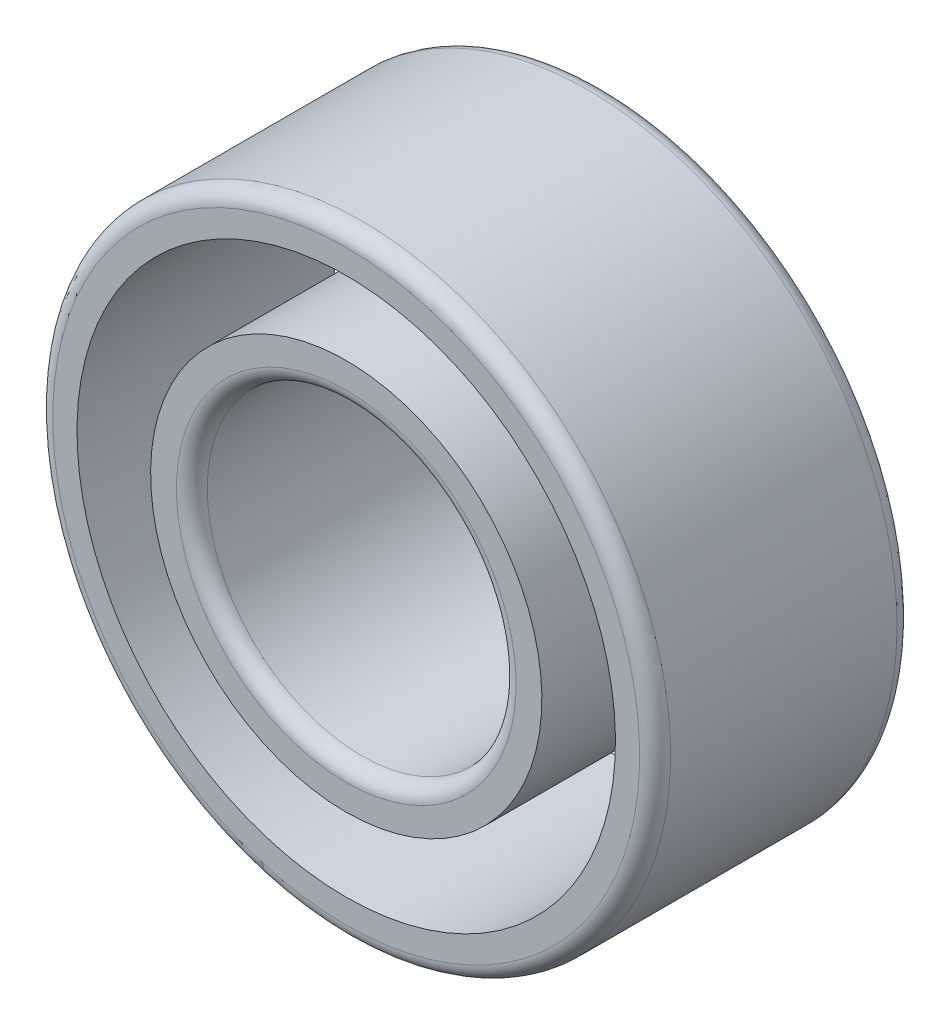
SolidWorks part; units mm, degrees
ref_plane "Front Plane" through (0, 0, 0) normal (0, 0, 1) x (1, 0, 0)
ref_plane "Top Plane" through (0, 0, 0) normal (0, 1, 0) x (1, 0, 0)
ref_plane "Right Plane" through (0, 0, 0) normal (1, 0, 0) x (0, 0, -1)
sketch "Sketch1" plane through (0, 0, 0) normal (1, 0, 0) x (0, 0, -1)
  line L0 (-1.25, 0) -> (1.25, 0) construction
  line L1 (-1.25, 3) -> (-1.25, 0) construction
  line L2 (-1.25, 3) -> (1.25, 3)
  line L3 (-1.25, 3) -> (-1.25, 2.615)
  line L4 (-1.25, 2.615) -> (1.25, 2.615)
  line L5 (1.25, 3) -> (1.25, 2.615)
  line L6 (-1.25, 1.9) -> (1.25, 1.9)
  line L7 (-1.25, 1.9) -> (-1.25, 1.5)
  line L8 (-1.25, 1.5) -> (1.25, 1.5)
  line L9 (1.25, 1.9) -> (1.25, 1.5)
  line L10 (1.25, 3) -> (1.25, 0) construction
  point P3 (0, 0)
  point P12 (1.25, 1.5)
  point P13 (1.2483, 1.9)
  point P14 (1.25, 2.7166)
  point P15 (1.25, 2.6039)
  dimension "D1" = 3
  dimension "D2" = 6
  dimension "D3" = 3.8
  dimension "D4" = 2.5
  dimension "D5" = 2.5
  dimension "D6" = 5.23
revolve "Revolve1" add sketch "Sketch1" angle 360 about L0
fillet "Fillet1" radius 0.15 2 edges at (0, -3, -1.25) (0, -3, 1.25)
fillet "Fillet2" radius 0.15 2 edges at (0, -1.5, -1.25) (0, -1.5, 1.25)
